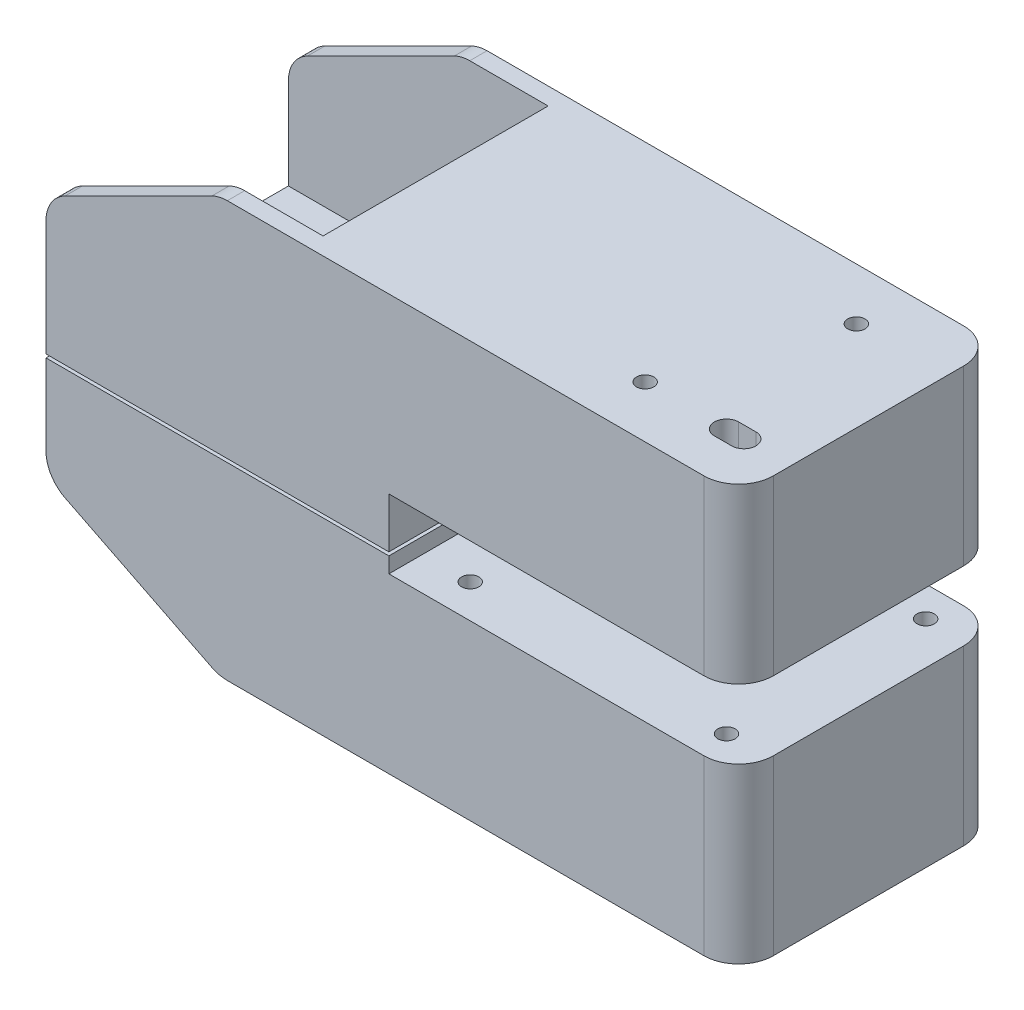
SolidWorks part; units mm, degrees
ref_plane "Front" through (0, 0, 0) normal (0, 0, 1) x (1, 0, 0)
ref_plane "Top" through (0, 0, 0) normal (0, 1, 0) x (1, 0, 0)
ref_plane "Right" through (0, 0, 0) normal (1, 0, 0) x (0, 0, -1)
sketch "Sketch1" plane through (0, 0, 0) normal (0, 1, 0) x (1, 0, 0)
  line L1 (-4.5, -4.5) -> (4.5, -4.5) construction
  line L2 (-4.5, -4.5) -> (-4.5, 4.5) construction
  line L3 (-4.5, 4.5) -> (4.5, 4.5) construction
  line L4 (4.5, -4.5) -> (4.5, 4.5) construction
  line L5 (-4.5, -4.5) -> (4.5, 4.5) construction
  line L6 (-4.5, 4.5) -> (4.5, -4.5) construction
  line L11 (-34.4, 7.5) -> (5.6, 7.5)
  line L12 (-34.4, 7.5) -> (-34.4, -7.5)
  line L13 (1.9, -4.5) -> (2.9, -4.5) construction
  line L14 (1.9, -3.8) -> (2.9, -3.8)
  line L15 (1.9, -5.2) -> (2.9, -5.2)
  line L16 (-34.4, -7.5) -> (5.6, -7.5)
  line L17 (5.6, 7.5) -> (5.6, -7.5)
  circle A0 centre (0.4, 4.5) radius 0.5
  circle A1 centre (-2.8, -4.5) radius 0.5
  circle A2 centre (1.9, -4.5) radius 0.5 construction
  circle A3 centre (2.9, -4.5) radius 0.5 construction
  arc A4 (1.9, -3.8) -> (1.9, -5.2) centre (1.9, -4.5) ccw
  arc A5 (2.9, -5.2) -> (2.9, -3.8) centre (2.9, -4.5) ccw
  point P0 (0, 0)
  point P14 (0, 0)
  point P19 (5.6, 0)
  point P21 (2.4, -4.5)
  dimension "D2" = 0.4
  dimension "D3" = 2.8
  dimension "D6" = 1
  dimension "D8" = 0.2
  dimension "D1" = 9
  dimension "D4" = 2.9
  dimension "D5" = 1
  dimension "D7" = 15
  dimension "D9" = 2.7
  dimension "D10" = 40
extrude "Boss-Extrude1" add sketch "Sketch1" along normal blind 3
sketch "Sketch2" plane through (0, 3, 0) normal (0, 1, 0) x (1, 0, 0)
  line L0 (2.9, -3.8) -> (1.9, -3.8) construction
  line L1 (1.9, -5.2) -> (2.9, -5.2) construction
  line L2 (2.9, -3.8) -> (1.9, -3.8)
  line L3 (1.9, -5.2) -> (2.9, -5.2)
  line L4 (-34.4, 7.5) -> (-34.4, -7.5)
  line L5 (-34.4, -7.5) -> (5.6, -7.5)
  line L6 (5.6, -7.5) -> (5.6, 7.5)
  line L7 (5.6, 7.5) -> (-34.4, 7.5)
  line L8 (-34.4, 7.5) -> (-34.4, 6.5)
  line L9 (-34.4, -7.5) -> (5.6, -7.5)
  line L10 (5.6, -7.5) -> (5.6, 7.5)
  line L11 (5.6, 7.5) -> (-34.4, 7.5)
  line L12 (-34.4, -6.5) -> (-34.4, -7.5)
  line L13 (-34.4, 6.5) -> (-19.4, 6.5)
  line L15 (-34.4, -6.5) -> (-19.4, -6.5)
  line L16 (-19.4, 6.5) -> (-19.4, -6.5)
  circle A0 centre (-2.8, -4.5) radius 0.5 construction
  arc A1 (2.9, -5.2) -> (2.9, -3.8) centre (2.9, -4.5) ccw construction
  arc A2 (1.9, -3.8) -> (1.9, -5.2) centre (1.9, -4.5) ccw construction
  circle A3 centre (0.4, 4.5) radius 0.5 construction
  circle A4 centre (-2.8, -4.5) radius 0.5
  arc A5 (2.9, -5.2) -> (2.9, -3.8) centre (2.9, -4.5) ccw
  arc A6 (1.9, -3.8) -> (1.9, -5.2) centre (1.9, -4.5) ccw
  circle A7 centre (0.4, 4.5) radius 0.5
  point P20 (-19.4, 0)
  dimension "D2" = 13
  dimension "D3" = 15
  dimension "D1" = 0
extrude "Boss-Extrude2" add sketch "Sketch2" along normal blind 7
sketch "Sketch3" plane through (0, 0, 0) normal (0, -1, 0) x (1, 0, 0)
  line L1 (-34.4, 7.5) -> (5.6, 7.5)
  line L2 (-34.4, 7.5) -> (-34.4, -7.5)
  line L3 (-34.4, -7.5) -> (5.6, -7.5)
  line L4 (5.6, 7.5) -> (5.6, -7.5)
extrude "Boss-Extrude3" add sketch "Sketch3" along normal blind 10 from offset 4 separate body
sketch "Sketch4" plane through (0, 0, 0) normal (0, -1, 0) x (1, 0, 0)
  line L0 (-34.4, -7.5) -> (5.6, -7.5) construction
  line L1 (-34.4, 7.5) -> (-14.6, 7.5)
  line L2 (-34.4, 7.5) -> (-34.4, -7.5)
  line L3 (-34.4, -7.5) -> (-14.6, -7.5)
  line L4 (-14.6, 7.5) -> (-14.6, -7.5)
  line L5 (5.6, 7.5) -> (5.6, -7.5) construction
  dimension "D1" = 20.2
extrude "Boss-Extrude4" add sketch "Sketch4" along normal blind 2.9
extrude "Boss-Extrude5" add sketch "Sketch4<2>" against normal offset from surface (0.9 mm away) 0.2 from surface up to face at (-24.5, -2.9, 0) starting at face at (-14.4, -4, 0)
sketch "Sketch4<2>" plane through (0, 0, 0) normal (0, -1, 0) x (1, 0, 0) same geometry as "Sketch4"
sketch "Sketch5" plane through (0, 3, 0) normal (0, 1, 0) x (1, 0, 0)
  line L4 (-34.4, -6.5) -> (-19.4, -6.5)
  line L5 (-19.4, -6.5) -> (-19.4, 6.5)
  line L6 (-19.4, 6.5) -> (-34.4, 6.5)
  line L7 (-34.4, 6.5) -> (-34.4, -6.5)
  line L8 (-34.4, -6.5) -> (-19.4, -6.5)
  line L9 (-19.4, -6.5) -> (-19.4, 6.5)
  line L10 (-19.4, 6.5) -> (-34.4, 6.5)
  line L11 (-34.4, 6.5) -> (-34.4, -6.5)
  dimension "D1" = 0
extrude "Cut-Extrude1" cut sketch "Sketch5" against normal offset from surface (4.5 mm away) 1.4 up to face at (-24.5, -2.9, 0)
extrude "Cut-Extrude2" cut sketch "Sketch5<2>" along normal offset from surface (9.5 mm away) 1.4 from surface up to face at (-24.5, -3.1, 0) starting at face at (-14.4, -14, 0)
sketch "Sketch5<2>" plane through (0, 3, 0) normal (0, 1, 0) x (1, 0, 0) same geometry as "Sketch5"
sketch "Sketch7" plane through (0, -4, 0) normal (0, 1, 0) x (1, 0, 0)
  line L0 (-34.4, 7.5) -> (5.6, 7.5) construction
  line L1 (5.6, -7.5) -> (-14.4, -7.5) construction
  line L2 (5.6, -7.5) -> (5.6, 7.5) construction
  line L3 (5.6, 7.5) -> (-14.4, 7.5) construction
  line L4 (-14.4, -7.5) -> (-14.4, 7.5) construction
  line L5 (5.6, 0) -> (-14.4, 0) construction
  circle A0 centre (3.15, 5.75) radius 0.5
  circle A1 centre (3.15, -5.75) radius 0.5
  circle A2 centre (-11.85, 5.55) radius 0.5
  circle A3 centre (-11.85, -5.55) radius 0.5
  circle A4 centre (-12.85, 0) radius 0.5
  circle A5 centre (-12.85, -2) radius 0.5
  circle A6 centre (-12.85, 2) radius 0.5
  point P9 (-14.4, 0)
  point P24 (0, 0)
  point P25 (0, 0)
  point P26 (0, 0)
  dimension "D2" = 17.55
  dimension "D3" = 2.55
  dimension "D6" = 1.55
  dimension "D8" = 1
  dimension "D1" = 20
  dimension "D4" = 5.55
  dimension "D5" = 5.75
  dimension "D7" = 2
extrude "Cut-Extrude3" cut sketch "Sketch7" against normal up to surface (10 mm away) up to face at (-20.65, -14, 0)
chamfer "Chamfer1" distance 5 distance2 10 2 edges at (-34.4, 10, 7) (-34.4, 10, -7) first distance on face at (-34.4, 3.9, 0)
fillet "Fillet2" radius 2 4 edges at (-34.4, 5, 7) (-34.4, 5, -7) (-24.4, 10, 7) (-24.4, 10, -7)
chamfer "Chamfer2" distance 5 distance2 10 2 edges at (-34.4, -14, -7) (-34.4, -14, 7) first distance on face at (-34.4, -8.9, 0)
fillet "Fillet3" radius 2 4 edges at (-24.4, -14, 7) (-24.4, -14, -7) (-34.4, -9, -7) (-34.4, -9, 7)
fillet "Fillet4" radius 2 2 edges at (5.6, 5, -7.5) (5.6, 5, 7.5)
fillet "Fillet5" radius 2 2 edges at (5.6, -9, -7.5) (5.6, -9, 7.5)
